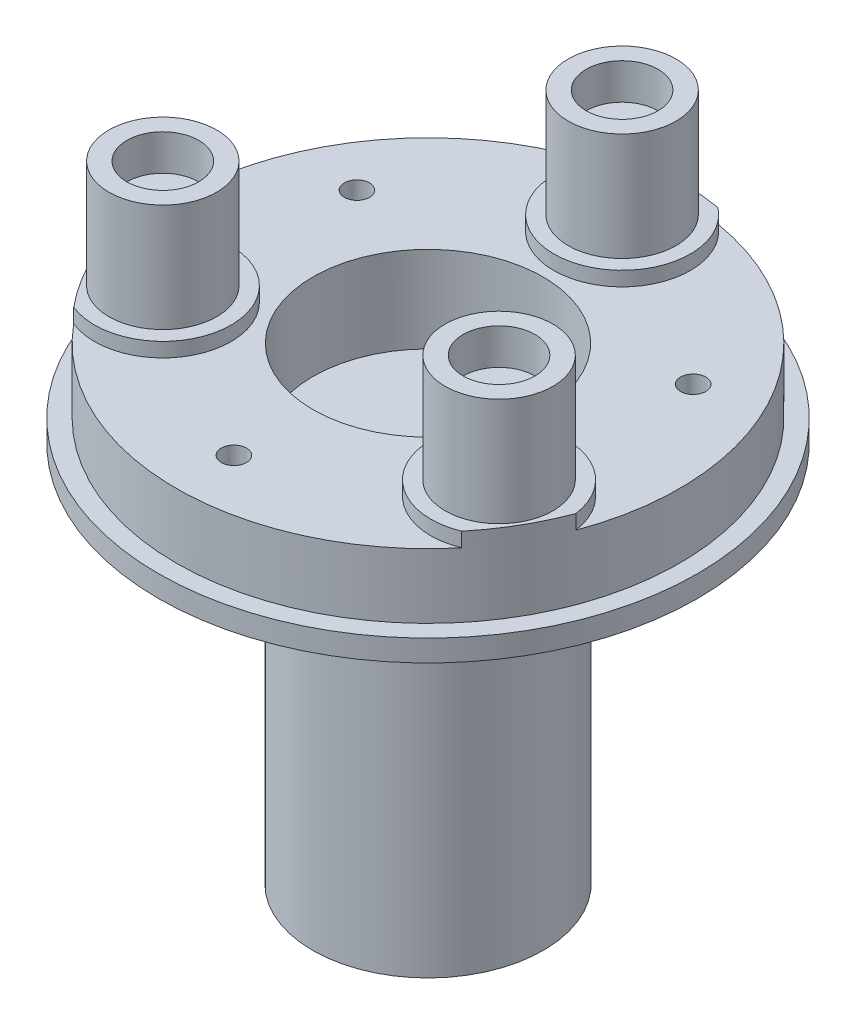
SolidWorks part; units mm, degrees
ref_plane "Front Plane" through (0, 0, 0) normal (0, 0, 1) x (1, 0, 0)
ref_plane "Top Plane" through (0, 0, 0) normal (0, 1, 0) x (1, 0, 0)
ref_plane "Right Plane" through (0, 0, 0) normal (1, 0, 0) x (0, 0, -1)
sketch "Sketch1" plane through (0, 0, 0) normal (0, 1, 0) x (1, 0, 0)
  line L0 (0, 0) -> (0, 44.6523) construction
  circle A4 centre (0, 0) radius 37.5
  circle A5 centre (0, 0) radius 35
  arc A6 (-10.4425, 33.4059) -> (10.4425, 33.4059) centre (0, 30) ccw
  circle A7 centre (0, 0) radius 35
  arc A8 (34.1516, -7.6594) -> (23.7091, -25.7465) centre (25.9808, -15) ccw
  arc A9 (-23.7091, -25.7465) -> (-34.1516, -7.6594) centre (-25.9808, -15) ccw
  point P17 (0, 0)
  dimension "D1" = 75
  dimension "D2" = 70
  dimension "D3" = 30
  dimension "D4" = 3
extrude "Boss-Extrude1" add sketch "Sketch1" along normal blind 3 contours A4
extrude "Boss-Extrude2" add sketch "Sketch1<3>" along normal blind 12 contours A5
sketch "Sketch1<3>" plane through (0, 0, 0) normal (0, 1, 0) x (1, 0, 0) same geometry as "Sketch1"
sketch "Sketch13" plane through (0, 12, 0) normal (0, 1, 0) x (1, 0, 0)
  circle A0 centre (0, 0) radius 16
  dimension "D1" = 32
extrude "Cut-Extrude6" cut sketch "Sketch13" against normal through all
sketch "Sketch24" plane through (0, 12, 0) normal (0, 1, 0) x (1, 0, 0)
  line L0 (0, 0) -> (0, 27.027) construction
  arc A0 (-5.813, 34.5139) -> (5.813, 34.5139) centre (0, 27) ccw
  circle A1 centre (0, 0) radius 35
  arc A2 (32.7964, -12.2227) -> (26.9834, -22.2912) centre (23.3827, -13.5) ccw
  arc A3 (-26.9834, -22.2912) -> (-32.7964, -12.2227) centre (-23.3827, -13.5) ccw
  point P15 (0, 0)
  circle M8 centre (0, 0) radius 35
  dimension "D1" = 19
  dimension "D4" = 70
  dimension "D2" = 27
  dimension "D3" = 3
extrude "Boss-Extrude9" add sketch "Sketch24" along normal blind 2 contours A1 A3 | A0 M8 | A1 A2 region at (0, 12, -26.6249) region at (-23.0578, 12, 13.3124) region at (23.0578, 12, 13.3124)
sketch "Sketch25" plane through (0, 14, 0) normal (0, 1, 0) x (1, 0, 0)
  line L0 (0, 0) -> (0, 55.8426) construction
  circle A0 centre (0, 27) radius 7.5
  circle A1 centre (23.3827, -13.5) radius 7.5
  circle A2 centre (-23.3827, -13.5) radius 7.5
  point P11 (0, 0)
  dimension "D2" = 15
  dimension "D1" = 27
  dimension "D3" = 3
extrude "Boss-Extrude10" add sketch "Sketch25" along normal blind 15
sketch "Sketch26" plane through (0, 29, 0) normal (0, 1, 0) x (1, 0, 0)
  line L0 (0, 0) -> (0, 38.3857) construction
  circle A0 centre (0, 27) radius 5
  circle A1 centre (23.3827, -13.5) radius 5
  circle A2 centre (-23.3827, -13.5) radius 5
  point P11 (0, 0)
  dimension "D2" = 10
  dimension "D1" = 27
  dimension "D3" = 3
extrude "Cut-Extrude9" cut sketch "Sketch26" against normal blind 5
hole_wizard "CBORE for M3 Pan Head Machine Screw1" positions "Sketch27" profile "Sketch28" counterbore size "M3" standard "ANSI Metric" end condition through all
sketch "Sketch27" plane through (0, 0, 0) normal (0, -1, 0) x (-1, 0, 0)
  point P0 (0, 27)
  point P9 (23.3827, -13.5)
  point P10 (-23.3827, -13.5)
  dimension "D1" = 27
  dimension "D2" = 3
sketch "Sketch28" plane through (0, 0, -27) normal (1, 0, 0) x (0, 0, -1)
  line L0 (0, 0) -> (0, 29)
  line L1 (0, 29) -> (1.8, 29)
  line L3 (1.8, 29) -> (1.8, 2.4)
  line L4 (3.5, 2.4) -> (1.8, 2.4)
  line L5 (3.5, 2.4) -> (3.5, 0.025)
  line L6 (3.5, 0.025) -> (3.525, 0)
  line L7 (3.525, 0) -> (0, 0)
  line L8 (-3.5, 0.025) -> (-3.525, 0) construction
  line L11 (0, -6.35) -> (0, 107.95) construction
  dimension "Thru Hole Dia." = 3.6
  dimension "Thru Hole Depth" = 29
  dimension "C'Bore Dia." = 7
  dimension "C'Bore Depth" = 2.4
  dimension "Near C'Sink Dia." = 7.05
  dimension "Near C'Sink Angle" = 90
sketch "Sketch29" plane through (0, 12, 0) normal (0, 1, 0) x (1, 0, 0)
  line L0 (0, 0) -> (23.3827, 13.5) construction
  line L1 (0, 0) -> (0, 14.4601) construction
  circle A0 centre (23.3827, 13.5) radius 1.75
  circle A1 centre (0, -27) radius 1.75
  circle A2 centre (-23.3827, 13.5) radius 1.75
  point P11 (0, 0)
  dimension "D3" = 3.5
  dimension "D1" = 60
  dimension "D2" = 27
  dimension "D4" = 3
extrude "Cut-Extrude10" cut sketch "Sketch29" against normal through all
sketch "Sketch30" plane through (0, 12, 0) normal (0, -1, 0) x (1, 0, 0)
  circle A0 centre (0, 0) radius 16
sketch "Sketch31" plane through (0, 0, 0) normal (0, -1, 0) x (1, 0, 0)
  circle A0 centre (0, 0) radius 16.05
extrude "Boss-Extrude11" add sketch "Sketch31" along normal blind 53.11 separate body
sketch "Sketch32" plane through (0, 0, 0) normal (0, -1, 0) x (1, 0, 0)
  circle A0 centre (0, 0) radius 16
  circle A1 centre (0, 0) radius 18
  dimension "D1" = 36
extrude "Boss-Extrude12" add sketch "Sketch32" along normal blind 1.11
